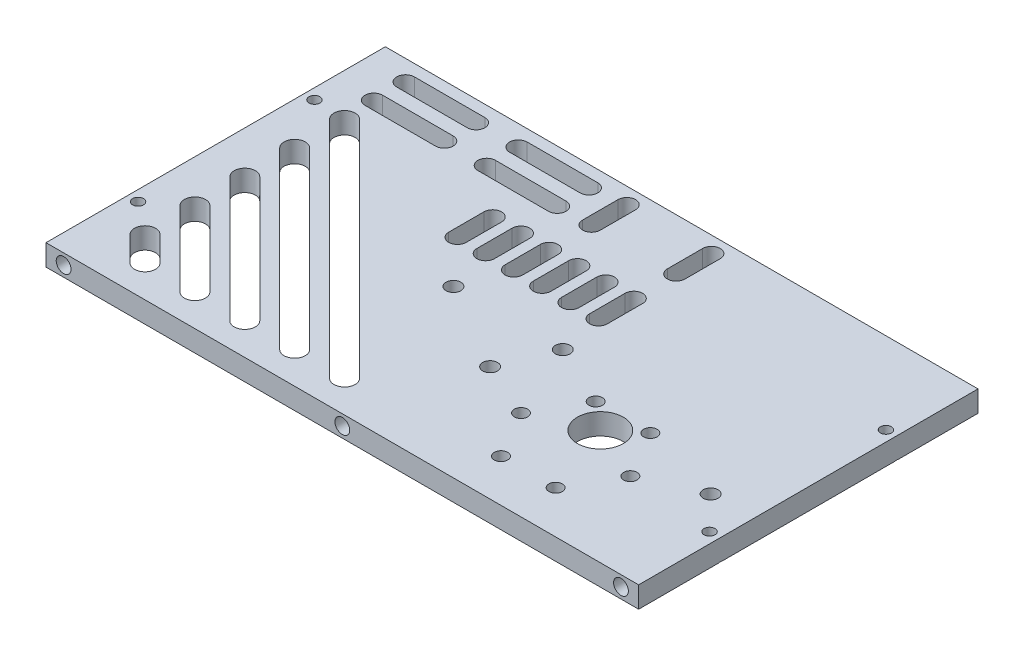
SolidWorks part; units mm, degrees
ref_plane "Front Plane" through (0, 0, 0) normal (1, 0, 0) x (0, 1, 0)
ref_plane "Top Plane" through (0, 0, 0) normal (0, 0, 1) x (0, 1, 0)
ref_plane "Right Plane" through (0, 0, 0) normal (0, 1, 0) x (-1, 0, 0)
sketch "Sketch1" plane through (0, 0, 0) normal (0, 1, 0) x (-1, 0, 0)
  line L3 (168, 0) -> (0, 0)
  line L10 (0, 96.2019) -> (168, 96.2019)
  line L15 (168, 96.2019) -> (168, 0)
  line L17 (0, 96.2019) -> (0, 0)
  point P16 (-5.5507, 58)
  point P19 (0, 0)
  point P27 (168, 0)
  dimension "D1" = 168
  dimension "D3" = 96.2019
extrude "Boss-Extrude1" add sketch "Sketch1" along normal blind 6 contours L10 L17 L3 L15 region at (-84, 0, 48.1009)
sketch "Sketch2" plane through (0, 0, 0) normal (0, -1, 0) x (1, 0, 0)
  line L0 (-93.9294, 6) -> (46.9505, 6) construction
  line L1 (-153.4835, 90.2019) -> (20.1803, 90.2019) construction
  line L2 (-28.5825, 49.2019) -> (48.7007, 49.2019) construction
  line L3 (-61.85, 63.025) -> (-61.85, 73.1366) construction
  line L4 (-168, 96.2019) -> (-168, 0) construction
  line L5 (-99.2651, 52.2019) -> (-68.3113, 52.2019) construction
  line L6 (-84, 47.6039) -> (-84, 23.5623) construction
  line L7 (-24.85, 55.8014) -> (-24.85, 50055.8014) construction
  line L8 (-10, 20.1758) -> (-10, 54.1601) construction
  line L9 (-156, 65.9887) -> (-134.7868, 87.2019) construction
  line L10 (-158.1213, 68.11) -> (-136.9081, 89.3232)
  line L11 (-153.8787, 63.8674) -> (-132.6655, 85.0806)
  line L12 (-156, 51.8466) -> (-120.6447, 87.2019) construction
  line L13 (-158.1213, 53.9679) -> (-122.766, 89.3232)
  line L14 (-153.8787, 49.7252) -> (-118.5233, 85.0806)
  line L15 (-156, 37.7044) -> (-106.5025, 87.2019) construction
  line L16 (-158.1213, 39.8257) -> (-108.6238, 89.3232)
  line L17 (-153.8787, 35.5831) -> (-104.3812, 85.0806)
  line L18 (-156, 23.5623) -> (-92.3604, 87.2019) construction
  line L19 (-158.1213, 25.6836) -> (-94.4817, 89.3232)
  line L20 (-153.8787, 21.441) -> (-90.2391, 85.0806)
  line L21 (-159, 102.2536) -> (-159, -2.1913) construction
  line L22 (0, 96.2019) -> (0, 0) construction
  line L23 (-43.35, 4.2203) -> (-43.35, -100.2246) construction
  line L24 (-156, 80.1308) -> (-148.9289, 87.2019) construction
  line L25 (-143.2721, 74.474) -> (-140.4437, 71.6456) construction
  line L26 (-136.201, 67.4029) -> (-133.3726, 64.5745) construction
  line L27 (-129.1299, 60.3318) -> (-126.3015, 57.5034) construction
  line L28 (-158.1213, 82.2522) -> (-151.0503, 89.3232)
  line L29 (-153.8787, 78.0095) -> (-146.8076, 85.0806)
  line L30 (-147.5147, 78.7166) -> (-150.3431, 81.545) construction
  line L31 (-168, 96.2019) -> (-168, 0) construction
  line L32 (-168, 0) -> (0, 0) construction
  line L33 (-43.35, 70.7019) -> (-43.35, 9.0934) construction
  line L35 (0, 96.2019) -> (-168, 96.2019) construction
  line L36 (0, 96.2019) -> (0, 0) construction
  circle A7 centre (-43.35, 63.7019) radius 6.5
  circle A9 centre (-43.35, 70.7019) radius 18.5 construction
  arc A11 (-158.1213, 68.11) -> (-153.8787, 63.8674) centre (-156, 65.9887) ccw
  arc A12 (-132.6655, 85.0806) -> (-136.9081, 89.3232) centre (-134.7868, 87.2019) ccw
  arc A13 (-158.1213, 53.9679) -> (-153.8787, 49.7252) centre (-156, 51.8466) ccw
  arc A14 (-118.5233, 85.0806) -> (-122.766, 89.3232) centre (-120.6447, 87.2019) ccw
  arc A15 (-158.1213, 39.8257) -> (-153.8787, 35.5831) centre (-156, 37.7044) ccw
  arc A16 (-104.3812, 85.0806) -> (-108.6238, 89.3232) centre (-106.5025, 87.2019) ccw
  arc A17 (-158.1213, 25.6836) -> (-153.8787, 21.441) centre (-156, 23.5623) ccw
  arc A18 (-90.2391, 85.0806) -> (-94.4817, 89.3232) centre (-92.3604, 87.2019) ccw
  arc A19 (-158.1213, 82.2522) -> (-153.8787, 78.0095) centre (-156, 80.1308) ccw
  arc A20 (-146.8076, 85.0806) -> (-151.0503, 89.3232) centre (-148.9289, 87.2019) ccw
  circle A21 centre (-43.35, 70.7019) radius 15.5 construction
  circle A22 centre (-58.85, 70.7019) radius 1.9
  circle A23 centre (-51.1, 84.1253) radius 1.9
  circle A24 centre (-35.6, 84.1253) radius 1.9
  circle A25 centre (-27.85, 70.7019) radius 1.9
  circle A26 centre (-35.6, 57.2785) radius 1.9
  circle A27 centre (-51.1, 57.2785) radius 1.9
  circle A32 centre (-43.35, 63.7019) radius 31.25 construction
  circle A33 centre (-74.6, 63.7019) radius 2.1
  circle A34 centre (-43.35, 94.9519) radius 2.1 construction
  circle A35 centre (-12.1, 63.7019) radius 2.1
  circle A36 centre (-43.35, 32.4519) radius 2.1 construction
  circle A37 centre (-68.5, 49.2019) radius 2.1
  circle A38 centre (-99.5, 49.2019) radius 2.1
  point P24 (-152.4645, 83.6664)
  point P45 (-145.3934, 76.5953)
  point P50 (-138.3223, 69.5242)
  point P57 (-131.2513, 62.4532)
  point P64 (-124.1802, 55.3821)
  dimension "D14" = 31
  dimension "D15" = 3.8
  dimension "D2" = 37
  dimension "D6" = 13
  dimension "D3" = 62.5
  dimension "D9" = 4.2
  dimension "D7" = 45
  dimension "D8" = 6
  dimension "D11" = 4
  dimension "D13" = 7
  dimension "D5" = 6
  dimension "D10" = 6
  dimension "D4" = 43.2019
  dimension "D17" = 10
  dimension "D19" = 10
  dimension "D20" = 9
  dimension "D12" = 31
  dimension "D21" = 3
  dimension "D16" = 6
  dimension "D18" = 4
extrude "Cut-Extrude1" cut sketch "Sketch2" against normal up to next
sketch "Sketch3" plane through (0, 0, 0) normal (0, 0, -1) x (1, 0, 0)
  line L2 (0, -3) -> (50000, -3) construction
  line L3 (0, -6) -> (0, 0) construction
  line L4 (-168, -6) -> (-168, 0) construction
  line L5 (-84, 0) -> (-84, -6) construction
  line L6 (-168, 0) -> (0, 0) construction
  line L7 (-168, -6) -> (0, -6) construction
  circle A0 centre (-5, -3) radius 2.1
  circle A1 centre (-163, -3) radius 2.1
  circle A2 centre (-84, -3) radius 2.1
  point P11 (0, -3)
  dimension "D1" = 4.2
  dimension "D3" = 5
  dimension "D2" = 5
extrude "Cut-Extrude2" cut sketch "Sketch3" against normal blind 15
extrude "Cut-Extrude3" cut sketch "Sketch3<3>" along normal blind 15 from surface starting at face at (-84, 3, 96.2019)
sketch "Sketch3<3>" plane through (0, 0, 0) normal (0, 0, -1) x (1, 0, 0) same geometry as "Sketch3"
sketch "Sketch4" plane through (0, 0, 0) normal (0, -1, 0) x (1, 0, 0)
  line L0 (-168, 48.1009) -> (0, 48.1009) construction
  line L1 (-165, 73.1009) -> (-3, 73.1009) construction
  line L2 (-165, 73.1009) -> (-165, 23.1009) construction
  line L3 (-165, 23.1009) -> (-3, 23.1009) construction
  line L4 (-3, 73.1009) -> (-3, 23.1009) construction
  line L5 (-168, 96.2019) -> (-168, 0) construction
  line L6 (0, 96.2019) -> (0, 0) construction
  circle A0 centre (-165, 73.1009) radius 1.55
  circle A1 centre (-165, 23.1009) radius 1.55
  circle A2 centre (-3, 23.1009) radius 1.55
  circle A3 centre (-3, 73.1009) radius 1.55
  dimension "D1" = 3.1
  dimension "D2" = 3
  dimension "D3" = 3
  dimension "D4" = 50
extrude "Cut-Extrude4" cut sketch "Sketch4" against normal up to next
sketch "Sketch5" plane through (0, 0, 0) normal (0, -1, 0) x (1, 0, 0)
  line L0 (-156.5, 14.7811) -> (-136.5, 14.7811) construction
  line L1 (-156.5, 17.2811) -> (-136.5, 17.2811)
  line L2 (-156.5, 12.2811) -> (-136.5, 12.2811)
  line L3 (-130.5, 20.5623) -> (-130.5, 0) construction
  line L6 (-168, 20.5623) -> (0, 20.5623) construction
  line L7 (-168, 96.2019) -> (-168, 0) construction
  line L8 (0, 96.2019) -> (0, 0) construction
  line L9 (-156.5, 5.7811) -> (-136.5, 5.7811) construction
  line L10 (-156.5, 8.2811) -> (-136.5, 8.2811)
  line L11 (-156.5, 3.2811) -> (-136.5, 3.2811)
  line L12 (-111, 36.5623) -> (-111, 26.5623) construction
  line L15 (-108.5, 36.5623) -> (-108.5, 26.5623)
  line L18 (-168, 10.2811) -> (0, 10.2811) construction
  line L19 (-159, 23.5623) -> (-159, 0) construction
  line L20 (-168, 0) -> (0, 0) construction
  line L21 (-104.5, 14.7811) -> (-124.5, 14.7811) construction
  line L22 (-104.5, 17.2811) -> (-124.5, 17.2811)
  line L23 (-104.5, 12.2811) -> (-124.5, 12.2811)
  line L24 (-113.5, 36.5623) -> (-113.5, 26.5623)
  line L27 (-104.5, 5.7811) -> (-124.5, 5.7811) construction
  line L28 (-104.5, 8.2811) -> (-124.5, 8.2811)
  line L29 (-104.5, 3.2811) -> (-124.5, 3.2811)
  line L30 (-103, 36.5623) -> (-103, 26.5623) construction
  line L33 (-100.5, 36.5623) -> (-100.5, 26.5623)
  line L34 (-105.5, 36.5623) -> (-105.5, 26.5623)
  line L35 (-95, 36.5623) -> (-95, 26.5623) construction
  line L36 (-92.5, 36.5623) -> (-92.5, 26.5623)
  line L37 (-97.5, 36.5623) -> (-97.5, 26.5623)
  line L38 (-87, 36.5623) -> (-87, 26.5623) construction
  line L39 (-84.5, 36.5623) -> (-84.5, 26.5623)
  line L40 (-89.5, 36.5623) -> (-89.5, 26.5623)
  line L41 (-79, 36.5623) -> (-79, 26.5623) construction
  line L42 (-76.5, 36.5623) -> (-76.5, 26.5623)
  line L43 (-81.5, 36.5623) -> (-81.5, 26.5623)
  line L44 (-71, 36.5623) -> (-71, 26.5623) construction
  line L45 (-68.5, 36.5623) -> (-68.5, 26.5623)
  line L46 (-73.5, 36.5623) -> (-73.5, 26.5623)
  line L51 (-113.5, 0) -> (-68.5, 0) construction
  line L52 (-113.5, 0) -> (-113.5, 39.0623) construction
  line L53 (-113.5, 39.0623) -> (-68.5, 39.0623) construction
  line L54 (-68.5, 0) -> (-68.5, 39.0623) construction
  line L69 (-71, 4.5623) -> (-71, 14.5623) construction
  line L70 (-68.5, 4.5623) -> (-68.5, 14.5623)
  line L71 (-73.5, 4.5623) -> (-73.5, 14.5623)
  line L72 (-79, 4.5623) -> (-79, 14.5623) construction
  line L73 (-76.5, 4.5623) -> (-76.5, 14.5623) construction
  line L74 (-81.5, 4.5623) -> (-81.5, 14.5623) construction
  line L75 (-87, 4.5623) -> (-87, 14.5623) construction
  line L76 (-84.5, 4.5623) -> (-84.5, 14.5623) construction
  line L77 (-89.5, 4.5623) -> (-89.5, 14.5623) construction
  line L78 (-95, 4.5623) -> (-95, 14.5623) construction
  line L79 (-92.5, 4.5623) -> (-92.5, 14.5623)
  line L80 (-97.5, 4.5623) -> (-97.5, 14.5623)
  line L81 (-103, 4.5623) -> (-103, 14.5623) construction
  line L82 (-100.5, 4.5623) -> (-100.5, 14.5623) construction
  line L83 (-105.5, 4.5623) -> (-105.5, 14.5623) construction
  line L84 (-111, 4.5623) -> (-111, 14.5623) construction
  line L85 (-108.5, 4.5623) -> (-108.5, 14.5623) construction
  line L86 (-113.5, 4.5623) -> (-113.5, 14.5623) construction
  arc A0 (-156.5, 17.2811) -> (-156.5, 12.2811) centre (-156.5, 14.7811) ccw
  arc A1 (-136.5, 12.2811) -> (-136.5, 17.2811) centre (-136.5, 14.7811) ccw
  arc A4 (-158.1213, 25.6836) -> (-153.8787, 21.441) centre (-156, 23.5623) ccw construction
  arc A5 (-156.5, 8.2811) -> (-156.5, 3.2811) centre (-156.5, 5.7811) ccw
  arc A6 (-136.5, 3.2811) -> (-136.5, 8.2811) centre (-136.5, 5.7811) ccw
  arc A11 (-104.5, 17.2811) -> (-104.5, 12.2811) centre (-104.5, 14.7811) cw
  arc A12 (-124.5, 12.2811) -> (-124.5, 17.2811) centre (-124.5, 14.7811) cw
  arc A15 (-104.5, 8.2811) -> (-104.5, 3.2811) centre (-104.5, 5.7811) cw
  arc A16 (-124.5, 3.2811) -> (-124.5, 8.2811) centre (-124.5, 5.7811) cw
  arc A19 (-108.5, 36.5623) -> (-113.5, 36.5623) centre (-111, 36.5623) ccw
  arc A20 (-113.5, 26.5623) -> (-108.5, 26.5623) centre (-111, 26.5623) ccw
  arc A21 (-100.5, 36.5623) -> (-105.5, 36.5623) centre (-103, 36.5623) ccw
  arc A22 (-105.5, 26.5623) -> (-100.5, 26.5623) centre (-103, 26.5623) ccw
  arc A23 (-92.5, 36.5623) -> (-97.5, 36.5623) centre (-95, 36.5623) ccw
  arc A24 (-97.5, 26.5623) -> (-92.5, 26.5623) centre (-95, 26.5623) ccw
  arc A25 (-84.5, 36.5623) -> (-89.5, 36.5623) centre (-87, 36.5623) ccw
  arc A26 (-89.5, 26.5623) -> (-84.5, 26.5623) centre (-87, 26.5623) ccw
  arc A27 (-76.5, 36.5623) -> (-81.5, 36.5623) centre (-79, 36.5623) ccw
  arc A28 (-81.5, 26.5623) -> (-76.5, 26.5623) centre (-79, 26.5623) ccw
  arc A29 (-68.5, 36.5623) -> (-73.5, 36.5623) centre (-71, 36.5623) ccw
  arc A30 (-73.5, 26.5623) -> (-68.5, 26.5623) centre (-71, 26.5623) ccw
  arc A44 (-68.5, 4.5623) -> (-73.5, 4.5623) centre (-71, 4.5623) cw
  arc A45 (-73.5, 14.5623) -> (-68.5, 14.5623) centre (-71, 14.5623) cw
  arc A46 (-76.5, 4.5623) -> (-81.5, 4.5623) centre (-79, 4.5623) cw construction
  arc A47 (-81.5, 14.5623) -> (-76.5, 14.5623) centre (-79, 14.5623) cw construction
  arc A48 (-84.5, 4.5623) -> (-89.5, 4.5623) centre (-87, 4.5623) cw construction
  arc A49 (-89.5, 14.5623) -> (-84.5, 14.5623) centre (-87, 14.5623) cw construction
  arc A50 (-92.5, 4.5623) -> (-97.5, 4.5623) centre (-95, 4.5623) cw
  arc A51 (-97.5, 14.5623) -> (-92.5, 14.5623) centre (-95, 14.5623) cw
  arc A52 (-100.5, 4.5623) -> (-105.5, 4.5623) centre (-103, 4.5623) cw construction
  arc A53 (-105.5, 14.5623) -> (-100.5, 14.5623) centre (-103, 14.5623) cw construction
  arc A54 (-108.5, 4.5623) -> (-113.5, 4.5623) centre (-111, 4.5623) cw construction
  arc A55 (-113.5, 14.5623) -> (-108.5, 14.5623) centre (-111, 14.5623) cw construction
  point P2 (-146.5, 14.7811)
  point P11 (-114.5, 14.7811)
  point P26 (-146.5, 5.7811)
  point P31 (-111, 31.5623)
  point P40 (-103, 31.5623)
  point P55 (-95, 31.5623)
  point P62 (-114.5, 5.7811)
  point P69 (-87, 31.5623)
  point P76 (-79, 31.5623)
  point P83 (-71, 31.5623)
  point P138 (-71, 9.5623)
  point P145 (-79, 9.5623)
  point P152 (-87, 9.5623)
  point P159 (-95, 9.5623)
  point P166 (-103, 9.5623)
  point P173 (-111, 9.5623)
  dimension "D1" = 2
  dimension "D2" = 5
  dimension "D3" = 4
  dimension "D4" = 20
  dimension "D5" = 6
  dimension "D6" = 5
  dimension "D7" = 10
  dimension "D8" = 6
  dimension "D10" = 3
  dimension "D9" = 6
extrude "Cut-Extrude5" cut sketch "Sketch5" against normal up to next
chamfer "Chamfer1" distance 1.5 distance2 2 4 edges at (-3, 0, 71.551) (-3, 0, 21.5509) (-165, 0, 21.5509) (-165, 0, 71.551) first distance on face at (-79, 0, 31.5623)
equation "\"MotorDriverLength\"= 60mm"
equation "\"MotorLength\"= 60"
equation "\"MotorDriverWidth\"=44"
equation "\"MotorWidth\"= 37"
equation "\"InnerWallThickness\"=3"
equation "\"BatteryWidth\"= 60"
equation "\"OuterWallThickness\" = 6"
equation "\"CompartmentHeight\"=37"
equation "\"CompartmentWidth\"= \"MotorDriverLength\""
equation "\"MotorDiameter\"=37"
equation "\"BatteryHeight\"=24.2019"
equation "\"MotorDriverHeight\"=28"
equation "\"CircuitHeight\"=30"
equation "\"FanThickness\"= 10"
equation "\"FanHeight\"=50"
equation "\"D1@Boss-Extrude1\" = \"OuterWallThickness\""
equation "\"MotorShaftHole\"=12"
equation "\"BearingBore\"=10"
equation "\"MinShinWidth\"= 20"
equation "\"ShinThickness\"=10"
equation "\"PivotDistance\"=30"
equation "\"ThighLength\"= 150"
equation "\"HipBore\"=27"
equation "\"ThighThickness\"=10"
equation "\"MaxBending\"=135"
equation "\"MaxStretchingAngle\"= 50"
equation "\"ThighJointDistance\"=157.485"
equation "\"ShinLength\"=120"
equation "\"BearingDiameter\"= 10"
equation "\"D2@Sketch2\"=\"MotorDiameter\""
equation "\"D6@Sketch2\"=\"MotorShaftHole\"+1"
equation "\"D5@Sketch2\"=\"OuterWallThickness\""
equation "\"D10@Sketch2\"=\"OuterWallThickness\""
equation "\"D4@Sketch2\"=\"BatteryHeight\"+\"OuterWallThickness\"*1.5+10"
equation "\"GearboxDiameter\"= 62.5"
equation "\"D1@Sketch1\" = \"ChessisInnerWidth\""
equation "\"ChessisInnerWidth\"= \"OuterWallThickness\" * 2 + \"MotorDriverLength\" + \"MotorDiameter\" + \"InnerWallThickness\" * 3 + \"CircuitLength\""
equation "\"CircuitLength\"=50"
equation "\"D3@Sketch1\" = \"ChessisHeight\""
equation "\"D3@Sketch2\"=\"GearboxDiameter\""
equation "\"D17@Sketch2\"=\"OuterWallThickness\"+4"
equation "\"D20@Sketch2\"=\"OuterWallThickness\"+3"
equation "\"ChessisHeight\"= \"BatteryHeight\" + 10 + \"InnerWallThickness\" + \"MotorDiameter\" + 10 + \"OuterWallThickness\" * 2"
equation "\"D3@Sketch4\"=\"OuterWallThickness\"/2"
equation "\"D2@Sketch4\"=\"OuterWallThickness\"/2"
